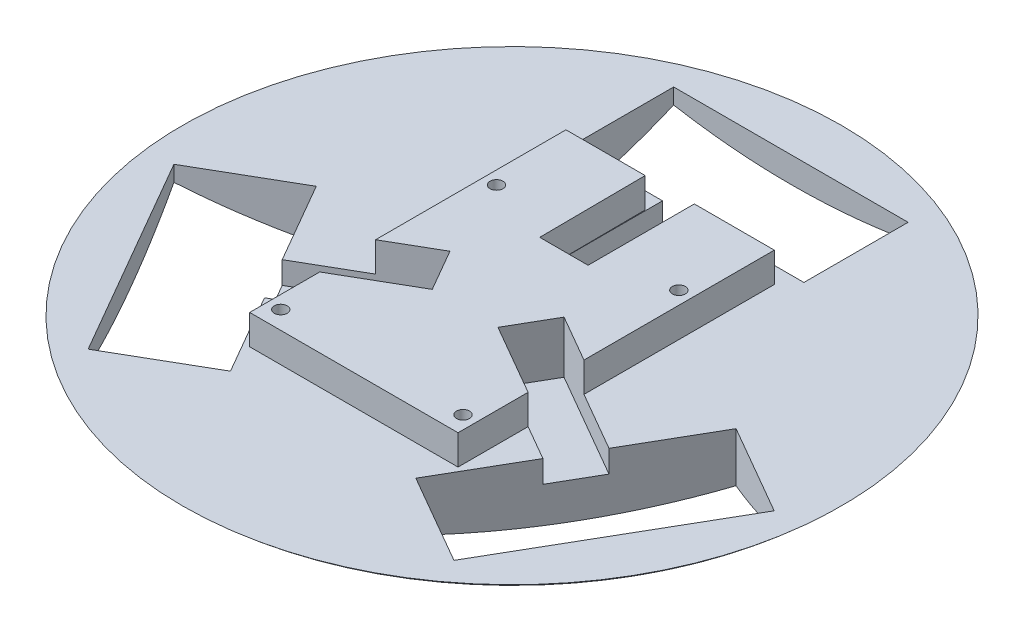
SolidWorks part; units mm, degrees
ref_plane "Front Plane" through (0, 0, 0) normal (0, 0, 1) x (1, 0, 0)
ref_plane "Top Plane" through (0, 0, 0) normal (0, 1, 0) x (1, 0, 0)
ref_plane "Right Plane" through (0, 0, 0) normal (1, 0, 0) x (0, 0, -1)
sketch "Sketch2" plane through (0, 0, 0) normal (0, 1, 0) x (1, 0, 0)
  line L0 (0, -68.0098) -> (0, 65.7503) construction
  line L1 (-31.5, 74.9495) -> (31.5, 74.9495)
  line L2 (-31.5, 74.9495) -> (-31.5, 46.9495)
  line L3 (-31.5, 46.9495) -> (31.5, 46.9495)
  line L4 (31.5, 74.9495) -> (31.5, 46.9495)
  line L5 (-31.5, 74.9495) -> (31.5, 46.9495) construction
  line L6 (-31.5, 46.9495) -> (31.5, 74.9495) construction
  line L7 (-70.2148, 0) -> (95.7201, 0) construction
  line L8 (0, 0) -> (-72.5813, -41.9048) construction
  line L9 (0, 0) -> (72.5813, -41.9048) construction
  line L10 (80.6581, -10.1949) -> (49.1581, -64.7545)
  line L11 (56.4094, 3.8051) -> (24.9094, -50.7545)
  line L12 (80.6581, -10.1949) -> (56.4094, 3.8051)
  line L13 (49.1581, -64.7545) -> (24.9094, -50.7545)
  line L14 (-49.1581, -64.7545) -> (-80.6581, -10.1949)
  line L15 (-24.9094, -50.7545) -> (-56.4094, 3.8051)
  line L16 (-49.1581, -64.7545) -> (-24.9094, -50.7545)
  line L17 (-80.6581, -10.1949) -> (-56.4094, 3.8051)
  line L18 (-6.5, -8.0505) -> (6.5, 46.9495) construction
  line L19 (-6.5, 46.9495) -> (6.5, 46.9495)
  line L20 (-6.5, 46.9495) -> (-6.5, -8.0505)
  line L21 (-6.5, -8.0505) -> (6.5, -8.0505)
  line L22 (6.5, 46.9495) -> (6.5, -8.0505)
  line L23 (-6.5, 46.9495) -> (6.5, -8.0505) construction
  line L24 (31.4023, -15.1408) -> (6.5, -0.7634)
  line L25 (-6.1216, -8.0505) -> (0, 2.5524)
  line L26 (24.9023, -26.3991) -> (0, -12.0218)
  line L27 (-25.0514, -26.4852) -> (0, -12.0218)
  line L28 (0, 2.5524) -> (6.1216, -8.0505)
  line L29 (-33.4324, -16.3129) -> (-6.5, -0.7634)
  circle A2 centre (0, 0) radius 16 construction
  point P3 (0, 19.4495)
  point P4 (0, 46.9495)
  point P6 (0, 60.9495)
  point P13 (0, 0)
  point P33 (0, 0)
  point P41 (0, -4.5162)
  dimension "D1" = 55
  dimension "D2" = 13
  dimension "D3" = 32
  dimension "D5" = 63
  dimension "D6" = 120
  dimension "D7" = 28
  dimension "D8" = 3
  dimension "D4" = 3
sketch "Sketch3" plane through (0, 0, 0) normal (1, 0, 0) x (0, 0, -1)
  line L0 (0, 83.7838) -> (0, -101.0811) construction
  line L1 (-115.9459, 0) -> (127.2973, 0) construction
  line L5 (0, 20) -> (0, 0)
  line L6 (88.569, 20) -> (0, 20)
  arc A3 (84.754, 17.3868) -> (0, 0) centre (7.3808, 179.2865) cw
  arc A4 (84.754, 17.3868) -> (88.569, 20) centre (78.286, 30.9207) ccw
  point P13 (90, 5.0684)
  dimension "D5" = 179.4384
  dimension "D1" = 15
  dimension "D2" = 20
  dimension "D3" = 20
  dimension "D4" = 90
revolve "Revolve1" add sketch "Sketch3" angle 360 about L5
extrude "Cut-Extrude1" cut sketch "Sketch2" along normal blind 40 contours L3 L4 L1 L2 | L15 L17 L14 L16 | L11 L13 L10 L12
sketch "Sketch4" plane through (0, 20, 0) normal (0, 1, 0) x (1, 0, 0)
  line L1 (-6.5, 46.9495) -> (6.5, 46.9495)
  line L2 (-6.5, 46.9495) -> (-6.5, 13.9495)
  line L3 (-6.5, 13.9495) -> (6.5, 13.9495)
  line L4 (6.5, 46.9495) -> (6.5, 13.9495)
  line L5 (-6.5, 46.9495) -> (6.5, 13.9495) construction
  line L6 (-6.5, 13.9495) -> (6.5, 46.9495) construction
  line L7 (43.9094, -17.8456) -> (37.4094, -29.1039)
  line L8 (-56.4094, 3.8051) -> (-24.9094, -50.7545) construction
  line L9 (-31.5, 46.9495) -> (31.5, 46.9495) construction
  line L10 (56.4094, 3.8051) -> (24.9094, -50.7545) construction
  line L26 (43.9094, -17.8456) -> (15.3306, -1.3456)
  line L27 (37.4094, -29.1039) -> (8.8306, -12.6039)
  line L28 (15.3306, -1.3456) -> (8.8306, -12.6039)
  line L29 (-37.4094, -29.1039) -> (-43.9094, -17.8456)
  line L30 (-37.4094, -29.1039) -> (-8.8306, -12.6039)
  line L31 (-43.9094, -17.8456) -> (-15.3306, -1.3456)
  line L32 (-8.8306, -12.6039) -> (-15.3306, -1.3456)
  line L33 (49.1581, -64.7545) -> (41.827, -60.5219)
  line L34 (49.1581, -64.7545) -> (24.9094, -50.7545) construction
  line L35 (49.1581, -64.7545) -> (80.6581, -10.1949)
  line L36 (80.6581, -10.1949) -> (73.327, -5.9623)
  line L37 (80.6581, -10.1949) -> (56.4094, 3.8051) construction
  circle A0 centre (0, 0) radius 88.569 construction
  circle A1 centre (0, 0) radius 73.569 construction
  arc A2 (41.827, -60.5219) -> (73.327, -5.9623) centre (0, 0) ccw
  circle A3 centre (0, 0) radius 81.2999
  point P0 (0, 30.4495)
  point P5 (0, 46.9495)
  point P22 (0, 0)
  point P23 (0, 4.0327)
  point P32 (-2.3282, 4.0326)
  line M8 (-56.4094, 3.8051) -> (-24.9094, -50.7545)
  line M13 (24.9094, -50.7545) -> (56.4094, 3.8051)
  line M17 (31.5, 46.9495) -> (-31.5, 46.9495)
  dimension "D4" = 177.1379
  dimension "D5" = 147.1379
  dimension "D6" = 162.5998
  dimension "D1" = 13
  dimension "D2" = 33
  dimension "D3" = 15
extrude "Cut-Extrude2" cut sketch "Sketch4" against normal blind 6 contours L4 L2 L3 M17 | L30 L32 L31 M8 | L26 L28 L27 M13 region at (0, 20, -30.4495) region at (26.37, 20, 15.2247) region at (-26.37, 20, 15.2247)
sketch "Sketch5" plane through (0, 20, 0) normal (0, 1, 0) x (1, 0, 0)
  line L0 (-28, -23.6714) -> (-8.8306, -12.6039)
  line L1 (-28, 42.5) -> (-6.7113, 42.5)
  line L2 (-28, 42.5) -> (-28, -8.6603)
  line L3 (-28, -42.5) -> (28, -42.5)
  line L4 (28, 42.5) -> (28, -8.6603)
  line L5 (-28, 42.5) -> (28, -42.5) construction
  line L6 (-28, -42.5) -> (28, 42.5) construction
  line L7 (-37.4094, -29.1039) -> (-8.8306, -12.6039) construction
  line L8 (-8.8306, -12.6039) -> (-15.3306, -1.3456)
  line L9 (-15.3306, -1.3456) -> (-28, -8.6603)
  line L10 (-43.9094, -17.8456) -> (-15.3306, -1.3456) construction
  line L11 (28, -23.6714) -> (8.8306, -12.6039)
  line L12 (37.4094, -29.1039) -> (8.8306, -12.6039) construction
  line L13 (8.8306, -12.6039) -> (15.3306, -1.3456)
  line L14 (15.3306, -1.3456) -> (28, -8.6603)
  line L15 (-6.7113, 42.5) -> (-6.5, 13.9495)
  line L16 (-6.5, 13.9495) -> (6.5, 13.9495)
  line L17 (6.5, 13.9495) -> (6.5, 42.5)
  line L18 (6.5, 46.9495) -> (6.5, 13.9495) construction
  line L19 (6.5, 46.9495) -> (6.5, 13.9495) construction
  line L20 (-28, -23.6714) -> (-28, -42.5)
  line L21 (28, -23.6714) -> (28, -42.5)
  line L22 (6.5, 42.5) -> (28, 42.5)
  line L23 (0, 13.9495) -> (0, -42.8187) construction
  line L24 (-28, -8.6603) -> (28, -8.6603) construction
  circle A0 centre (-24.5, -37.6603) radius 1.75
  circle A1 centre (24.5, -37.6603) radius 1.75
  circle A2 centre (24.5, 20.3397) radius 1.75
  circle A3 centre (-24.5, 20.3397) radius 1.75
  point P0 (0, 0)
  dimension "D3" = 3.5
  dimension "D1" = 56
  dimension "D2" = 85
  dimension "D4" = 49
  dimension "D5" = 58
extrude "Boss-Extrude1" add sketch "Sketch5" along normal blind 8
